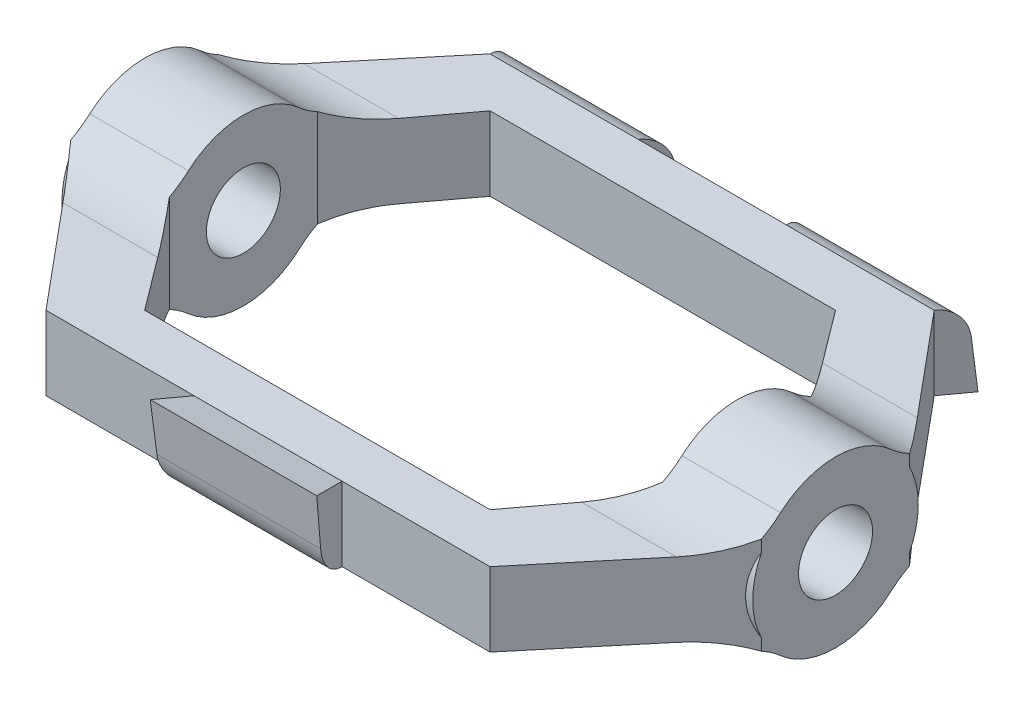
SolidWorks part; units mm, degrees
material "AISI 4340 Aço, normalizado"
ref_plane "Plano frontal" through (0, 0, 0) normal (0, 0, 1) x (1, 0, 0)
ref_plane "Plano superior" through (0, 0, 0) normal (0, 1, 0) x (1, 0, 0)
ref_plane "Plano direito" through (0, 0, 0) normal (1, 0, 0) x (0, 0, -1)
ref_plane "Plano1" through (-50, 0, 0) normal (1, 0, 0) x (0, 0, -1)
sketch "Esboço1" plane through (0, 0, 0) normal (0, 1, 0) x (1, 0, 0)
  line L0 (0, 0) -> (0, -28.2729) construction
  line L1 (-45, 45) -> (45, 45)
  line L2 (-45, -45) -> (45, -45)
  line L3 (-70, 15) -> (-70, -15) construction
  line L4 (-70, -15) -> (-45, -45)
  line L5 (-70, 15) -> (-45, 45)
  line L6 (-50, 15) -> (-70, 15)
  line L7 (-70, -15) -> (-50, -15)
  line L8 (-50, -15) -> (-35, -35)
  line L9 (-50, 15) -> (-35, 35)
  line L10 (-35, 35) -> (35, 35)
  line L11 (-35, -35) -> (35, -35)
  line L12 (70, 15) -> (70, -15) construction
  line L13 (50, 15) -> (35, 35)
  line L14 (50, -15) -> (35, -35)
  line L16 (-50, -15) -> (-70, -15)
  line L17 (45, -45) -> (70, -15)
  line L18 (45, 45) -> (70, 15)
  line L19 (70, 15) -> (50, 15)
  line L20 (70, -15) -> (50, -15)
  line L21 (39.3758, 0) -> (-39.3758, 0) construction
  point P8 (0, 45)
  point P9 (0, -45)
  point P13 (-70, 0)
  point P22 (70, 0)
  point P27 (0, 0)
  point P29 (0, -35)
  point P30 (0, 35)
  dimension "D1" = 45
  dimension "D2" = 10
  dimension "D3" = 30
  dimension "D4" = 90
  dimension "D5" = 10
  dimension "D6" = 20
  dimension "D7" = 70
  dimension "D8" = 15
extrude "Ressalto-extrusão1" add sketch "Esboço1" along normal mid plane 15 contours L17 L20 L14 L11 L8 L7 L4 L2 | L19 L18 L1 L5 L6 L9 L10 L13 region at (0, 0, -43.5682) region at (-56.4001, 0, 29.0834)
sketch "Esboço2" plane through (-50, 0, 0) normal (1, 0, 0) x (0, 0, -1)
  line L0 (15, 7.5) -> (-15, 7.5) construction
  line L1 (15, -7.5) -> (-15, -7.5) construction
  circle A0 centre (0, 0) radius 7.5
  circle A1 centre (0, 0) radius 16.7705
  dimension "D1" = 15
extrude "Ressalto-extrusão2" add sketch "Esboço2" against normal blind 20
mirror "Espelhar1" about plane through (0, 0, 0) normal (1, 0, 0) of "Ressalto-extrusão2"
fillet "Filete1" radius 20 8 edges at (-60, 7.5, -15) (-60, -7.5, 15) (-60, -7.5, -15) (-60, 7.5, 15) (60, 7.5, 15) (60, -7.5, 15) (60, -7.5, -15) (60, 7.5, -15)
sketch "Esboço3" plane through (0, 0, 45) normal (0, 0, 1) x (1, 0, 0)
  line L3 (-15, -7.5) -> (15, -7.5)
  line L4 (-45, -7.5) -> (45, -7.5) construction
  line L6 (-15, 7.5) -> (-15, -7.5)
  line L8 (15, 7.5) -> (15, -7.5)
  line L9 (15, 7.5) -> (-15, 7.5)
  point P0 (0, -7.5)
  point P1 (0, 7.5)
  point P2 (0, 0)
  point P5 (0, 0)
  point P12 (0, 0)
  point P15 (-15, 0)
  point P18 (15, 0)
  dimension "D2" = 30
sketch "Esboço4" plane through (0, 0, -45) normal (0, 0, -1) x (-1, 0, 0)
  line L0 (45, -7.5) -> (-45, -7.5) construction
  line L1 (-45, 7.5) -> (-15, 7.5)
  line L2 (-45, 7.5) -> (-45, -7.5)
  line L3 (-45, -7.5) -> (-15, -7.5)
  line L4 (-15, 7.5) -> (-15, -7.5)
  line L5 (0, 0) -> (0, -39.7615) construction
  line L6 (15, 7.5) -> (15, -7.5)
  line L7 (45, -7.5) -> (15, -7.5)
  line L8 (45, 7.5) -> (45, -7.5)
  line L9 (45, 7.5) -> (15, 7.5)
  dimension "D1" = 30
  dimension "D2" = 30
extrude "Ressalto-extrusão3" add sketch "Esboço3" along normal blind 7 draft 15 draft outward yes
sketch "Esboço8" plane through (0, 0, 0) normal (1, 0, 0) x (0, 0, -1)
  line L0 (-52, 0) -> (-51, 0) construction
  line L1 (-52, -9.3756) -> (-52, 9.3756) construction
  line L2 (200000, 0) -> (-200028.2729, 0) construction
  line L3 (-52, 9.3756) -> (-50.0556, -8.8546)
  line L4 (-52, -9.3756) -> (-45, -7.5) construction
  line L5 (-50.0556, -8.8546) -> (-52, -9.3756)
  line L6 (-52, -9.3756) -> (-52, 9.3756)
  dimension "D1" = 1
extrude "Ressalto-extrusão4" add sketch "Esboço4" along normal blind 7 draft 15 draft outward yes
extrude "Corte-extrusão1" cut sketch "Esboço8" against normal mid plane 33.76
sketch "Esboço7" plane through (0, 0, 0) normal (1, 0, 0) x (0, 0, -1)
  line L0 (52, 0) -> (51, 0) construction
  line L2 (200000, 0) -> (-200028.2729, 0) construction
  line L5 (52, 9.3756) -> (52, -9.3756)
  line L6 (52, -9.3756) -> (50.0556, 8.8546)
  line L7 (52, 9.3756) -> (45, 7.5) construction
  line L8 (50.0556, 8.8546) -> (52, 9.3756)
  dimension "D1" = 1
extrude "Corte-extrusão2" cut sketch "Esboço7" against normal mid plane 93.76
fillet "Filete4" radius 8 3 edges at (0, -8.8546, 50.0556) (30, 8.8546, -50.0556) (-30, 8.8546, -50.0556)
